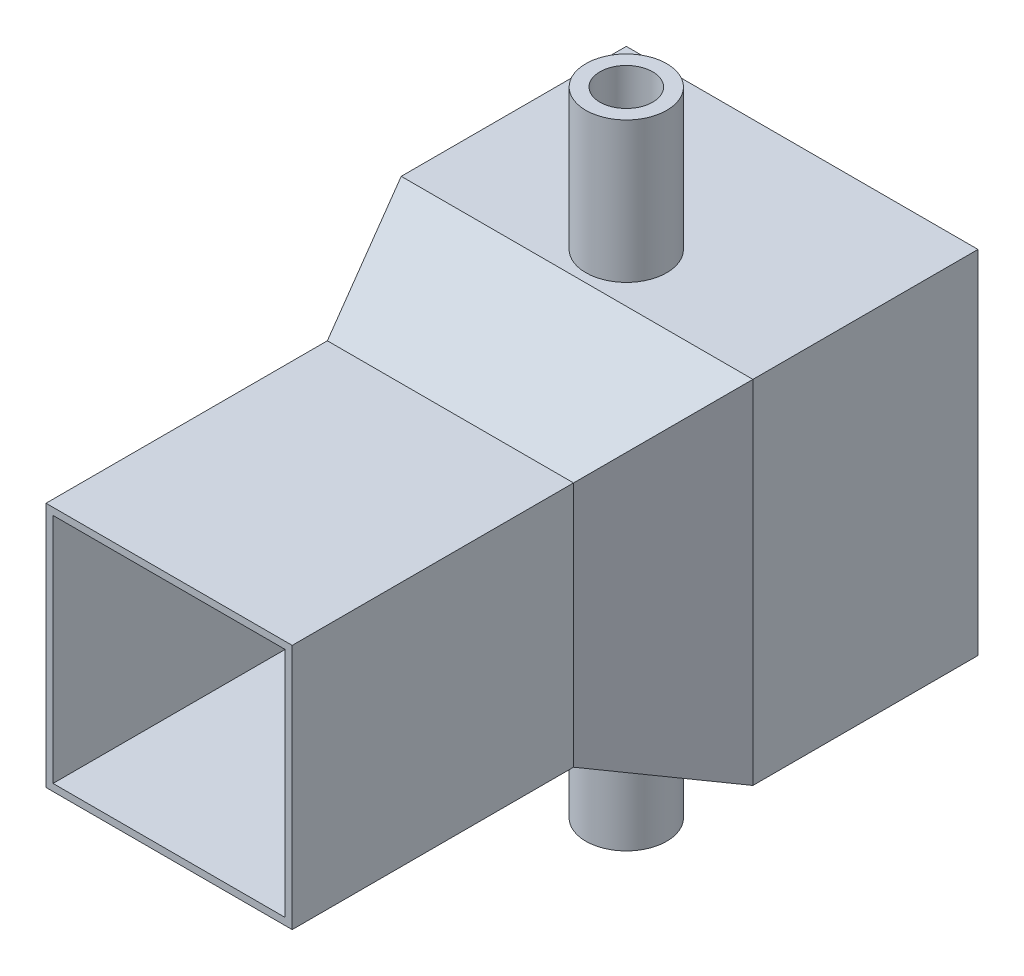
SolidWorks part; units mm, degrees
ref_plane "Front Plane" through (0, 0, 0) normal (0, 0, 1) x (1, 0, 0)
ref_plane "Top Plane" through (0, 0, 0) normal (0, 1, 0) x (1, 0, 0)
ref_plane "Right Plane" through (0, 0, 0) normal (1, 0, 0) x (0, 0, -1)
sketch "Sketch1" plane through (0, 0, 0) normal (0, 1, 0) x (1, 0, 0)
  circle A0 centre (0, 0) radius 3.75
  circle A1 centre (0, 0) radius 5.75
  dimension "D1" = 7.5
  dimension "D2" = 11.5
sketch "Sketch2" plane through (0, 0, 0) normal (0, 0, 1) x (1, 0, 0)
  line L0 (0, 0) -> (0, 20)
  line L1 (5.75, 0) -> (-5.75, 0) construction
  dimension "D1" = 20
sweep "Sweep1" add profiles "Sketch1" path "Sketch2"
ref_plane "Plane1" through (0, 20, 0) normal (0, 1, 0) x (1, 0, 0)
sketch "Sketch3" plane through (0, 20, 0) normal (0, 1, 0) x (1, 0, 0)
  line L1 (-25, -25) -> (25, -25)
  line L2 (-25, -25) -> (-25, 25)
  line L3 (-25, 25) -> (25, 25)
  line L4 (25, -25) -> (25, 25)
  line L5 (-25, -25) -> (25, 25) construction
  line L6 (-25, 25) -> (25, -25) construction
  circle A0 centre (0, 0) radius 4.7625
  circle A1 centre (0, 0) radius 5.7625
  point P0 (0, 0)
  dimension "D2" = 9.525
  dimension "D3" = 11.525
  dimension "D1" = 50
extrude "Boss-Extrude1" add sketch "Sketch3" along normal blind 50 separate body contours L4 L3 L2 L1
sketch "Sketch9" plane through (0, 0, 0) normal (1, 0, 0) x (0, 0, -1)
  line L0 (0, 0) -> (0, 70) construction
  line L1 (0, 35) -> (-15, 35) construction
  line L2 (-15, 35) -> (-55, 35)
  line L3 (-15, 35) -> (-25, 41.6332)
  line L4 (-25, 70) -> (-25, 20) construction
  line L5 (-55, 35) -> (-55, 43)
  line L6 (-25, 41.6332) -> (-55, 43)
  dimension "D1" = 70
  dimension "D2" = 15
  dimension "D3" = 40
  dimension "D4" = 12
  dimension "D5" = 8
sketch "Sketch12" plane through (0, 0, 25) normal (0, 0, 1) x (1, 0, 0)
  line L0 (0, 70) -> (0, 20) construction
  line L1 (-25, 70) -> (25, 70) construction
  line L2 (-25, 20) -> (25, 20) construction
  line L4 (-17.5, 27.5) -> (17.5, 27.5)
  line L5 (-17.5, 27.5) -> (-17.5, 62.5)
  line L6 (-17.5, 62.5) -> (17.5, 62.5)
  line L7 (17.5, 27.5) -> (17.5, 62.5)
  line L8 (-17.5, 27.5) -> (17.5, 62.5) construction
  line L9 (-17.5, 62.5) -> (17.5, 27.5) construction
  line L10 (-16.5, 28.5) -> (16.5, 28.5)
  line L11 (-16.5, 28.5) -> (-16.5, 61.5)
  line L12 (-16.5, 61.5) -> (16.5, 61.5)
  line L13 (16.5, 28.5) -> (16.5, 61.5)
  line L14 (-16.5, 28.5) -> (16.5, 61.5) construction
  line L15 (-16.5, 61.5) -> (16.5, 28.5) construction
  point P6 (0, 45)
  point P11 (0, 45)
  dimension "D1" = 35
  dimension "D2" = 33
extrude "Boss-Extrude3" add sketch "Sketch12" along normal blind 40
extrude "Cut-Extrude2" cut sketch "Sketch12<3>" against normal blind 2 contours L10 L13 L12 L11 region at (0, 45, 25)
sketch "Sketch12<3>" plane through (0, 0, 25) normal (0, 0, 1) x (1, 0, 0) same geometry as "Sketch12"
sketch "Sketch13" plane through (0, 62.5, 0) normal (0, 1, 0) x (1, 0, 0)
  line L0 (0, -65) -> (0, -55) construction
  line L1 (17.5, -65) -> (-17.5, -65) construction
  line L2 (-10, -65) -> (10, -65) construction
  line L3 (-17.5, -55) -> (-10, -65) construction
  line L4 (-17.5, -65) -> (-17.5, -25) construction
  line L5 (-17.5, -55) -> (17.5, -55) construction
  line L6 (17.5, -65) -> (17.5, -25) construction
  line L7 (17.5, -55) -> (10, -65) construction
  point P8 (0, -65)
  dimension "D1" = 10
  dimension "D2" = 10
sketch "Sketch14" plane through (25, 0, 0) normal (1, 0, 0) x (0, 0, -1)
  line L0 (-25, 70) -> (-7, 70)
  line L1 (-25, 70) -> (25, 70) construction
  line L2 (-7, 70) -> (-25, 62.5)
  line L3 (-25, 70) -> (-25, 62.5)
  line L4 (-25, 45) -> (25, 45) construction
  line L5 (-25, 70) -> (-25, 20) construction
  line L6 (25, 70) -> (25, 20) construction
  line L7 (-25, 20) -> (-25, 27.5)
  line L8 (-25, 20) -> (-7, 20)
  line L9 (-7, 20) -> (-25, 27.5)
  dimension "D1" = 18
extrude "Cut-Extrude3" cut sketch "Sketch14" against normal through all
sketch "Sketch15" plane through (0, 20, 0) normal (0, -1, 0) x (1, 0, 0)
  line L0 (-25, 25) -> (-25, 7)
  line L1 (-25, 7) -> (-25, 25) construction
  line L2 (-25, 7) -> (-17.5, 25)
  line L3 (-17.5, 25) -> (-25, 25)
  line L4 (0, 25) -> (0, 7) construction
  line L5 (-17.5, 25) -> (17.5, 25) construction
  line L6 (-25, 7) -> (25, 7) construction
  line L7 (17.5, 25) -> (25, 25)
  line L8 (25, 25) -> (25, 7)
  line L9 (25, 7) -> (17.5, 25)
  dimension "D1" = 18
extrude "Cut-Extrude4" cut sketch "Sketch15" against normal through all
shell "Shell2" thickness 2 removed face at (0, 45, 23)
sketch "Sketch17" plane through (0, 70, 0) normal (0, 1, 0) x (1, 0, 0)
  circle A0 centre (0, 0) radius 5.75
  circle A1 centre (0, 0) radius 3.75
  point P4 (0, 0)
  dimension "D1" = 11.5
  dimension "D2" = 7.5
extrude "Boss-Extrude4" add sketch "Sketch17" along normal blind 20
extrude "Cut-Extrude5" cut sketch "Sketch17<2>" against normal through all contours A1 region at (0, 70, 0)
sketch "Sketch17<2>" plane through (0, 70, 0) normal (0, 1, 0) x (1, 0, 0) same geometry as "Sketch17"
